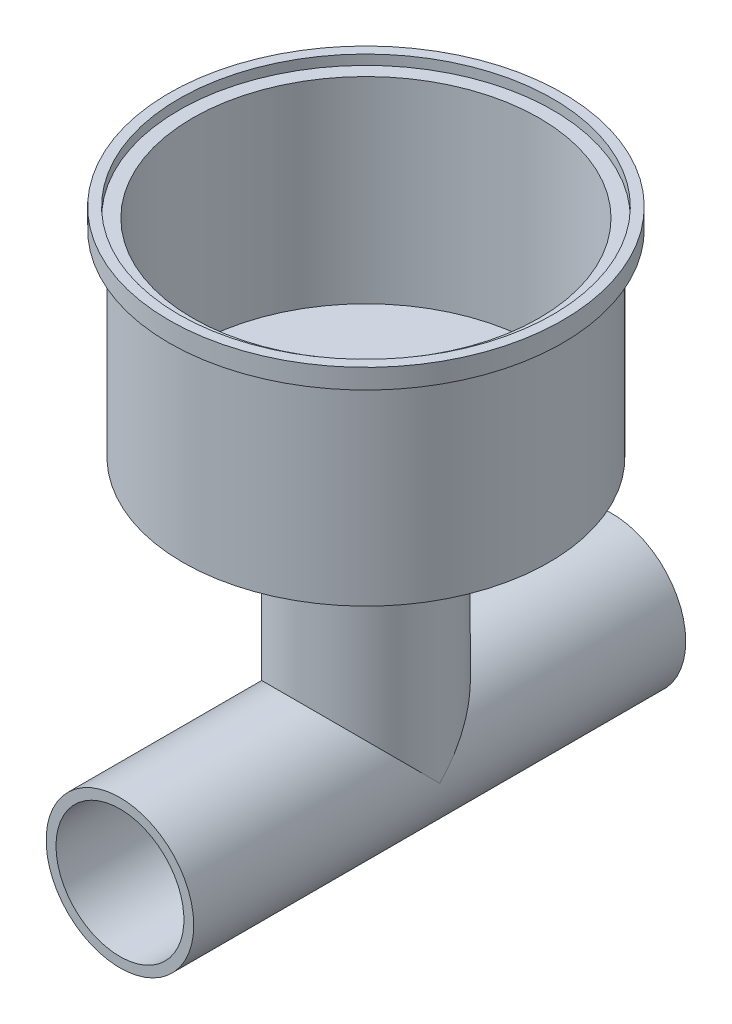
SolidWorks part; units mm, degrees
material "6061-T6 (SS)"
ref_plane "Płaszczyzna przednia" through (0, 0, 0) normal (0, 0, 1) x (1, 0, 0)
ref_plane "Płaszczyzna górna" through (0, 0, 0) normal (0, 1, 0) x (1, 0, 0)
ref_plane "Płaszczyzna prawa" through (0, 0, 0) normal (1, 0, 0) x (0, 0, -1)
sketch "Szkic1" plane through (0, 0, 0) normal (0, 0, 1) x (1, 0, 0)
  circle A0 centre (0, 0) radius 7.5
  dimension "D1" = 15
extrude "Dodanie-wyciągnięcie1" add sketch "Szkic1" along normal mid plane 50
sketch "Szkic3" plane through (0, 0, 0) normal (0, 1, 0) x (1, 0, 0)
  circle A0 centre (0, 0) radius 7.5
  dimension "D1" = 15
extrude "Dodanie-wyciągnięcie2" add sketch "Szkic3" along normal blind 25
sketch "Szkic4" plane through (0, 25, 0) normal (0, 1, 0) x (1, 0, 0)
  circle A0 centre (0, 0) radius 18.6139
extrude "Dodanie-wyciągnięcie3" add sketch "Szkic4" along normal blind 20
sketch "Szkic5" plane through (0, 45, 0) normal (0, 1, 0) x (1, 0, 0)
  circle A0 centre (0, 0) radius 20
  dimension "D1" = 40
extrude "Dodanie-wyciągnięcie4" add sketch "Szkic5" along normal blind 2
shell "Skorupa1" thickness 1 removed face at (0, 47, 20)
sketch "Szkic6" plane through (0, 0, -25) normal (0, 0, -1) x (-1, 0, 0)
  circle A0 centre (0, 0) radius 6.5
  dimension "D1" = 13
extrude "Wytnij-wyciągnięcie1" cut sketch "Szkic6" against normal through all
